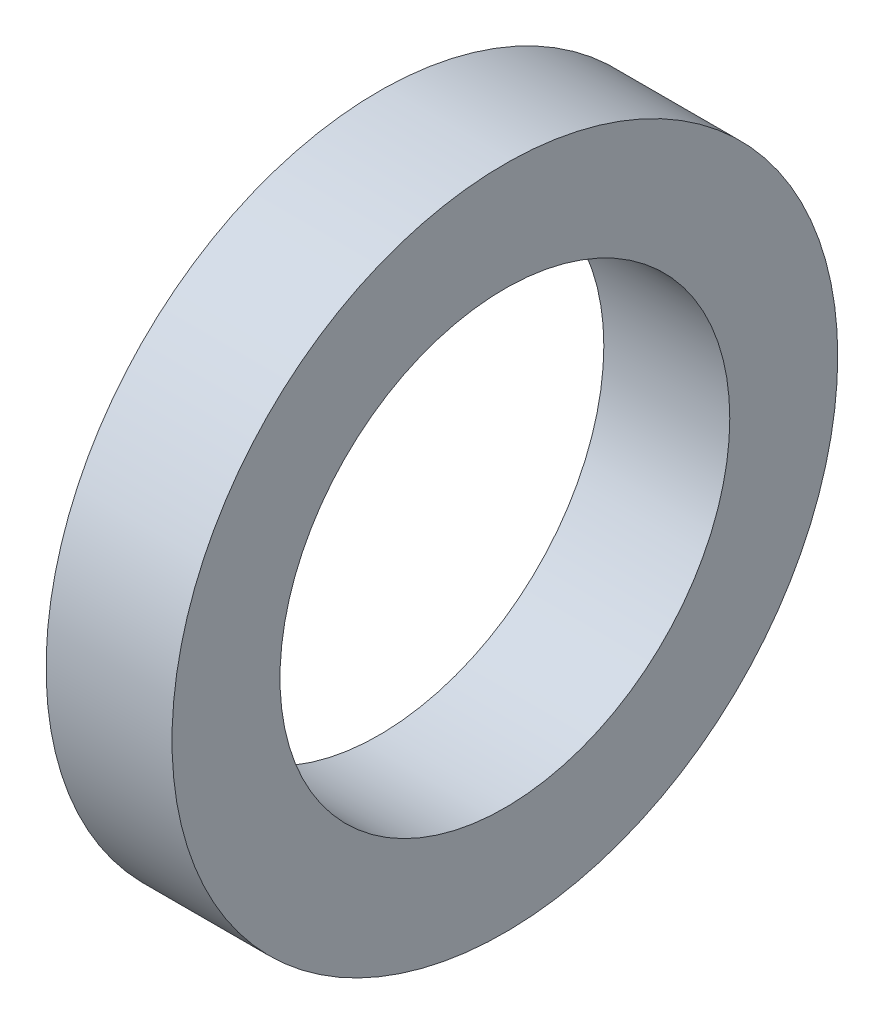
SolidWorks part; units mm, degrees
material "1023 Carbon Steel Sheet (SS)"
ref_plane "Front Plane" through (0, 0, 0) normal (0, 0, 1) x (1, 0, 0)
ref_plane "Top Plane" through (0, 0, 0) normal (0, 1, 0) x (1, 0, 0)
ref_plane "Right Plane" through (0, 0, 0) normal (1, 0, 0) x (0, 0, -1)
sketch "Sketch1" plane through (0, 0, 0) normal (1, 0, 0) x (0, 0, -1)
  circle A0 centre (0, 0) radius 18.5
  circle A1 centre (0, 0) radius 12.5
  dimension "D1" = 25
  dimension "D2" = 37
extrude "Boss-Extrude1" add sketch "Sketch1" along normal mid plane 7
ref_axis "Axis1" through (-3.85, 0, 0) along (1, 0, 0)
